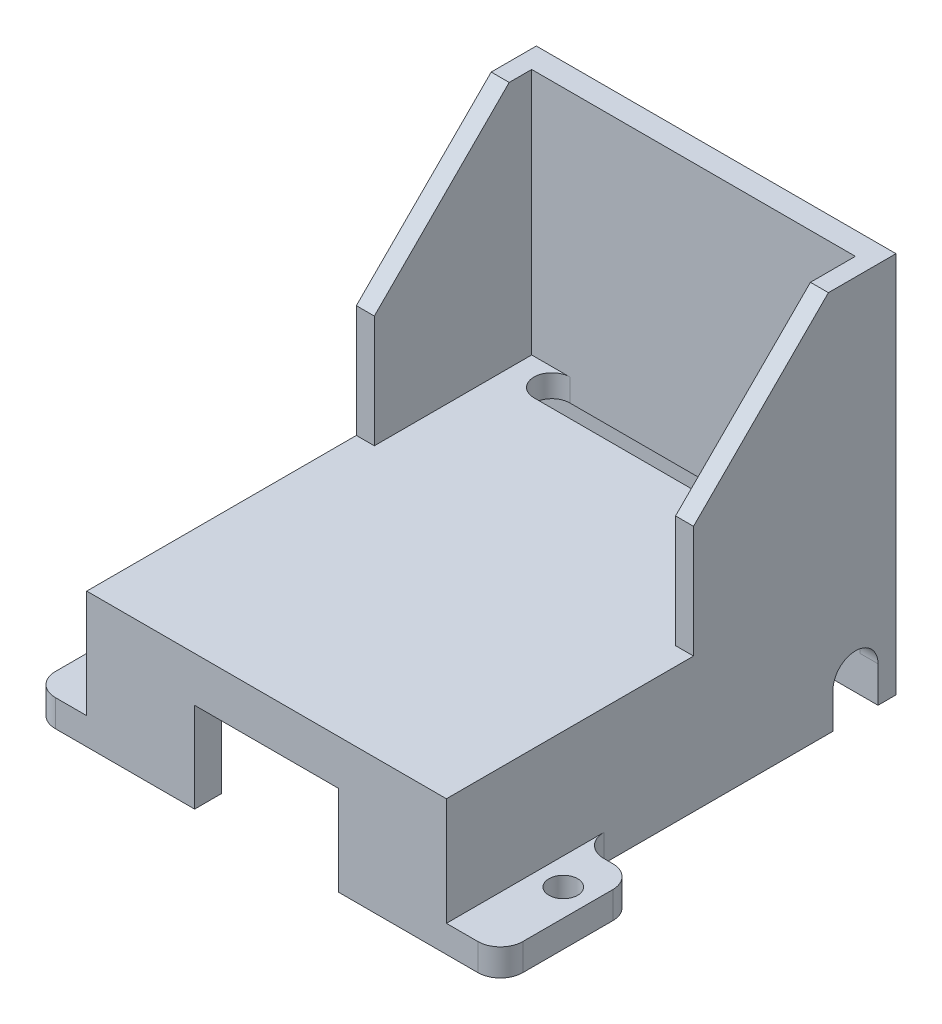
SolidWorks part; units mm, degrees
ref_plane "Front Plane" through (0, 0, 0) normal (0, 0, 1) x (1, 0, 0)
ref_plane "Top Plane" through (0, 0, 0) normal (0, 1, 0) x (1, 0, 0)
ref_plane "Right Plane" through (0, 0, 0) normal (1, 0, 0) x (0, 0, -1)
sketch "Sketch1" plane through (0, 0, 0) normal (0, 1, 0) x (1, 0, 0)
  line L1 (0, 0) -> (40, 0)
  line L2 (0, 0) -> (0, 50)
  line L3 (0, 50) -> (40, 50)
  line L4 (40, 0) -> (40, 50)
  dimension "D1" = 50
  dimension "D2" = 40
extrude "Boss-Extrude1" add sketch "Sketch1" along normal blind 15
sketch "Sketch2" plane through (0, 0, 0) normal (0, -1, 0) x (1, 0, 0)
  line L0 (0, 0) -> (40, 0) construction
  line L1 (12, 0) -> (28, 0)
  line L2 (12, 0) -> (12, -3)
  line L3 (12, -3) -> (28, -3)
  line L4 (28, 0) -> (28, -3)
  line L5 (40, -50) -> (0, -50) construction
  point P6 (20, -3)
  point P7 (20, -50)
  dimension "D1" = 16
  dimension "D2" = 3
extrude "Cut-Extrude1" cut sketch "Sketch2" against normal blind 10
sketch "Sketch3" plane through (0, 0, 0) normal (0, -1, 0) x (1, 0, 0)
  line L0 (12, -3) -> (28, -3) construction
  line L1 (2, -3) -> (38, -3)
  line L2 (2, -3) -> (2, -48)
  line L3 (2, -48) -> (38, -48)
  line L4 (38, -3) -> (38, -48)
  line L5 (0, -50) -> (0, 0) construction
  line L6 (40, 0) -> (40, -50) construction
  line L7 (40, -50) -> (0, -50) construction
  dimension "D1" = 2
  dimension "D2" = 2
  dimension "D3" = 2
extrude "Cut-Extrude2" cut sketch "Sketch3" against normal offset from surface (12.5 mm away) 2.5 up to face at (20, 15, -25)
sketch "Sketch4" plane through (0, 15, 0) normal (0, 1, 0) x (1, 0, 0)
  line L0 (40, 0) -> (40, 50) construction
  line L1 (0, 50) -> (40, 50)
  line L2 (0, 50) -> (0, 47.4843)
  line L3 (0, 47.4843) -> (40, 47.4843)
  line L4 (40, 50) -> (40, 47.4843)
extrude "Boss-Extrude2" add sketch "Sketch4" along normal blind 27.5
sketch "Sketch5" plane through (0, 15, 0) normal (0, 1, 0) x (1, 0, 0)
  line L0 (6.25, 45.4843) -> (13.75, 45.4843) construction
  line L1 (6.25, 47.4843) -> (13.75, 47.4843)
  line L2 (6.25, 43.4843) -> (13.75, 43.4843)
  line L3 (0, 47.4843) -> (40, 47.4843) construction
  line L4 (25.75, 45.4843) -> (33.25, 45.4843) construction
  line L5 (25.75, 47.4843) -> (33.25, 47.4843)
  line L6 (25.75, 43.4843) -> (33.25, 43.4843)
  line L7 (13.75, 43.4843) -> (25.75, 43.4843)
  line L8 (0, 0) -> (20, 0)
  line L9 (0, 0) -> (40, 0) construction
  line L10 (13.75, 47.4843) -> (25.75, 47.4843)
  line L11 (40, 0) -> (40, 47.4843) construction
  arc A0 (6.25, 47.4843) -> (6.25, 43.4843) centre (6.25, 45.4843) ccw
  arc A2 (25.75, 47.4843) -> (25.75, 43.4843) centre (25.75, 45.4843) ccw
  arc A3 (33.25, 43.4843) -> (33.25, 47.4843) centre (33.25, 45.4843) ccw
  point P2 (10, 45.4843)
  point P11 (29.5, 45.4843)
  point P23 (10, 0)
  line M9 (40, 47.4843) -> (0, 47.4843)
  dimension "D1" = 4
  dimension "D2" = 7.5
  dimension "D3" = 7.5
  dimension "D4" = 10.5
extrude "Cut-Extrude3" cut sketch "Sketch5" against normal through all contours L2 A0 M9 | L6 A3 A2 M9 region at (14.4292, 15, -45.4843) region at (29.5, 15, -45.4843)
sketch "Sketch6" plane through (0, 15, 0) normal (0, 1, 0) x (1, 0, 0)
  line L5 (0, 0) -> (40, 0) construction
  line L7 (0, 47.4843) -> (2, 47.4843)
  line L8 (0, 47.4843) -> (0, 29.9843)
  line L9 (0, 29.9843) -> (2, 29.9843)
  line L10 (2, 47.4843) -> (2, 29.9843)
  line L11 (40, 47.4843) -> (38, 47.4843)
  line L12 (40, 47.4843) -> (40, 27.4843)
  line L13 (40, 27.4843) -> (38, 27.4843)
  line L14 (38, 47.4843) -> (38, 27.4843)
  point P6 (20, 0)
  dimension "D2" = 17.5
extrude "Boss-Extrude3" add sketch "Sketch6" along normal blind 27.5
sketch "Sketch7" plane through (0, 0, 0) normal (-1, 0, 0) x (0, 0, 1)
  line L0 (-48, 0) -> (-48, 4)
  line L1 (-48, 12.5) -> (-48, 0) construction
  line L2 (-43, 4) -> (-43, 0)
  line L3 (-50, 0) -> (0, 0) construction
  arc A0 (-48, 4) -> (-43, 4) centre (-45.5, 4) cw
  line M7 (-50, 0) -> (0, 0)
  dimension "D1" = 5
  dimension "D2" = 4
extrude "Cut-Extrude5" cut sketch "Sketch7" against normal through all and the other way through all contours A0 L0 L2 M7 region at (0, 3.0079, -45.5)
sketch "Sketch8" plane through (40, 0, 0) normal (1, 0, 0) x (0, 0, -1)
  line L1 (0, 0) -> (15, 0)
  line L2 (0, 0) -> (0, 3)
  line L3 (0, 3) -> (15, 3)
  line L4 (15, 0) -> (15, 3)
  dimension "D1" = 3
  dimension "D2" = 15
extrude "Boss-Extrude4" add sketch "Sketch8" along normal blind 6
sketch "Sketch9" plane through (0, 3, 0) normal (0, 1, 0) x (1, 0, 0)
  line L0 (46, 0) -> (40, 0) construction
  circle A0 centre (43, 10) radius 1.6
  point P4 (43, 0)
  dimension "D1" = 3.2
  dimension "D2" = 10
extrude "Cut-Extrude6" cut sketch "Sketch9" against normal through all
ref_plane "Plane1" through (20, 0, 0) normal (-1, 0, 0) x (0, 0, 1)
mirror "Mirror1" about plane through (20, 0, 0) normal (-1, 0, 0) of "Cut-Extrude6", "Boss-Extrude4"
fillet "Fillet1" radius 2.5 6 edges at (0, 1.5, -15) (40, 1.5, -15) (46, 1.5, -15) (-6, 1.5, -15) (46, 1.5, 0) (-6, 1.5, 0)
chamfer "Chamfer3" distance 15 angle 45 2 edges at (1, 42.5, -29.9843) (39, 42.5, -27.4843)
